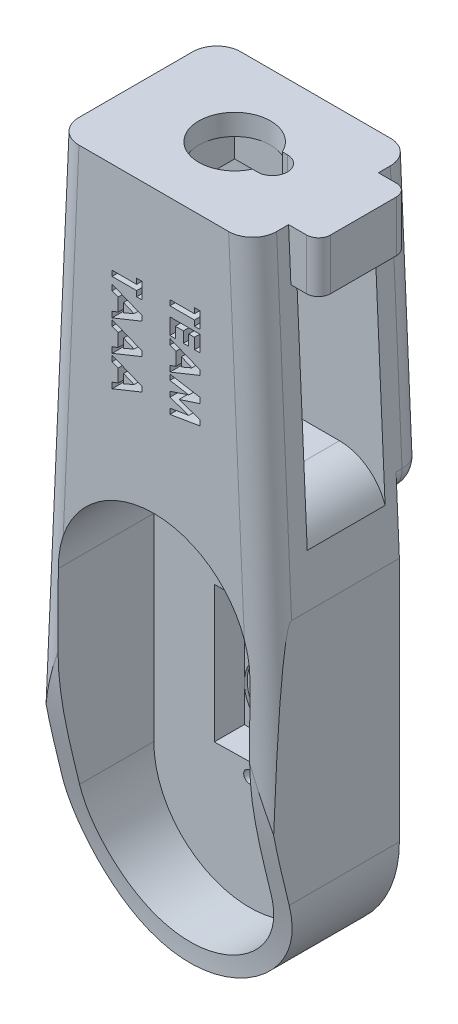
SolidWorks part; units mm, degrees
ref_plane "Front Plane" through (0, 0, 0) normal (0, 0, 1) x (1, 0, 0)
ref_plane "Top Plane" through (0, 0, 0) normal (0, 1, 0) x (1, 0, 0)
ref_plane "Right Plane" through (0, 0, 0) normal (1, 0, 0) x (0, 0, -1)
sketch "Sketch1" plane through (0, 0, 0) normal (0, 0, 1) x (1, 0, 0)
  line L5 (-19, -60) -> (19, -60)
  line L6 (-19, -60) -> (-19, 60)
  line L7 (-19, 60) -> (19, 60)
  line L8 (19, -60) -> (19, 60)
  dimension "D4" = 120
extrude "Boss-Extrude1" add sketch "Sketch1" along normal blind 11
ref_plane "Plane1" through (0, 0, 10) normal (0, 0, 1) x (1, 0, 0)
fillet "Fillet3" radius 19 2 edges at (19, -60, 5.5) (-19, -60, 5.5)
sketch "Sketch4" plane through (0, 0, 11) normal (0, 0, 1) x (1, 0, 0)
  line L0 (16, -41) -> (16, 57)
  line L1 (16, 57) -> (-16, 57)
  line L2 (-16, 57) -> (-16, -41)
  line L3 (19, -41) -> (19, 60)
  line L4 (19, 60) -> (-19, 60)
  line L5 (-19, 60) -> (-19, -41)
  line L6 (19, -41) -> (19, 60)
  line L7 (19, 60) -> (-19, 60)
  line L8 (-19, 60) -> (-19, -41)
  arc A0 (-16, -41) -> (0, -57) centre (0, -41) ccw
  arc A1 (0, -57) -> (16, -41) centre (0, -41) ccw
  arc A2 (-19, -41) -> (0, -60) centre (0, -41) ccw
  arc A3 (0, -60) -> (19, -41) centre (0, -41) ccw
  arc A4 (-19, -41) -> (0, -60) centre (0, -41) ccw
  arc A5 (0, -60) -> (19, -41) centre (0, -41) ccw
  dimension "D1" = 0
  dimension "D2" = 3
extrude "Boss-Extrude2" add sketch "Sketch4" along normal blind 8
sketch "Sketch6" plane through (0, 0, 0) normal (1, 0, 0) x (0, 0, -1)
  line L7 (-13, -60) -> (-17, -35)
  line L8 (-17, -35) -> (-19, -20)
  line L9 (-19, -41) -> (-19, 60) construction
  line L10 (-19, -20) -> (-19, -60)
  line L11 (-19, -41) -> (-19, -60) construction
  line L12 (-19, -60) -> (-13, -60)
  line L13 (-11, -60) -> (0, -60) construction
  spline S0 degree 3 poles (-19, -20) (-18.8828, -33.6175) (-12.1748, -46.2563) (-13, -60) knots 0 0 0 0 1 1 1 1
  dimension "D1" = 6
  dimension "D2" = 25
  dimension "D3" = 15
  dimension "D4" = 2
extrude "Cut-Extrude2" cut sketch "Sketch6" against normal through all both and the other way through all contours L8 L7 | L10 L12 L7 L8 region at (0, -47.6101, 16.9935) region at (0, -47.9061, 14.5246)
sketch "Sketch7" plane through (0, 0, 11) normal (0, 0, 1) x (1, 0, 0)
  line L0 (16, -20) -> (16, 57) construction
  line L1 (16, 8) -> (-16, 8)
  line L2 (16, 8) -> (16, 57)
  line L3 (16, 57) -> (-16, 57)
  line L4 (-16, 8) -> (-16, 57)
  dimension "D1" = 49
extrude "Boss-Extrude4" add sketch "Sketch7" along normal up to surface (8 mm away) up to face at (0, 19.25, 19)
sketch "Sketch8" plane through (0, 0, 0) normal (0, 0, -1) x (-1, 0, 0)
  line L0 (-19, 60) -> (19, 60)
  line L1 (19, 60) -> (19, -6.3108)
  line L2 (19, 60) -> (19, -41) construction
  line L3 (-19, 60) -> (-19, -7)
  line L4 (-19, -41) -> (-19, 60) construction
  line L7 (19, 8) -> (-19, 8)
  arc A0 (19, -6.3108) -> (-19, -7) centre (0.25, -20.4388) ccw
  line M2 (-19, 60) -> (-19, -41)
  line M6 (19, 60) -> (-19, 60)
  dimension "D1" = 23.4769
  dimension "D2" = 67
  dimension "D3" = 19.25
  dimension "D4" = 52
extrude "Boss-Extrude5" add sketch "Sketch8" along normal blind 8 contours L7 L1 M6 M2 region at (0, 34, 0)
sketch "Sketch24" plane through (0, 0, 0) normal (0, 0, -1) x (-1, 0, 0)
  line L3 (-19, 8) -> (-19, -41)
  line L4 (19, -41) -> (19, 8)
  line L5 (19, 8) -> (-19, 8)
  line L6 (-19, 8) -> (-19, -41)
  line L7 (19, -41) -> (19, 8)
  line L9 (19, 8) -> (-19, 8)
  arc A3 (-19, -41) -> (0, -60) centre (0, -41) ccw
  arc A6 (-19, -41) -> (0, -60) centre (0, -41) ccw
  arc A7 (0, -60) -> (19, -41) centre (0, -41) ccw
  arc A8 (0, -60) -> (19, -41) centre (0, -41) ccw
  dimension "D1" = 0
extrude "Boss-Extrude6" add sketch "Sketch24" along normal blind 3
sketch "Sketch3" plane through (0, 0, 10) normal (0, 0, 1) x (1, 0, 0)
  circle A6 centre (0, -10.975) radius 1
  circle A7 centre (0, -38.125) radius 1
  dimension "D1" = 10.975
  dimension "D2" = 27.15
extrude "Cut-Extrude1" cut sketch "Sketch3" against normal through all both and the other way through all
fillet "Fillet4" radius 16 2 edges at (-16, 8, 15) (16, 8, 15)
sketch "Sketch26" plane through (0, 60, 0) normal (0, 1, 0) x (1, 0, 0)
  line L4 (19, -19) -> (19, 8)
  line L5 (19, 8) -> (-19, 8)
  line L6 (-19, 8) -> (-19, -19)
  line L7 (-19, -19) -> (19, -19)
  line L8 (19, -19) -> (19, 8)
  line L10 (-19, 8) -> (-19, -19)
  line L11 (-19, -19) -> (19, -19)
  line L23 (19, 8) -> (-19, 8)
  dimension "D1" = 0
extrude "Cut-Extrude4" cut sketch "Sketch26" against normal blind 5
sketch "Sketch27" plane through (19, 0, 0) normal (1, 0, 0) x (0, 0, -1)
  line L0 (-19, 55) -> (8, 55) construction
  line L1 (-12, 45) -> (1, 45)
  line L2 (-12, 45) -> (-12, 14)
  line L3 (-12, 14) -> (1, 14)
  line L4 (1, 45) -> (1, 14)
  line L5 (-19, -20) -> (-19, 55) construction
  dimension "D1" = 10
  dimension "D2" = 31
  dimension "D3" = 13
  dimension "D4" = 7
extrude "Cut-Extrude5" cut sketch "Sketch27" against normal through all
sketch "Sketch29" plane through (0, 45, 0) normal (0, -1, 0) x (1, 0, 0)
  line L7 (-19, -1) -> (19, -1)
  line L8 (19, -1) -> (19, 12)
  line L9 (19, 19) -> (19, -8) construction
  line L10 (19, 12) -> (-19, 12)
  line L11 (-19, 12) -> (-19, -1)
extrude "Cut-Extrude7" cut sketch "Sketch29" against normal blind 1.5
sketch "Sketch28" plane through (0, 55, 0) normal (0, 1, 0) x (1, 0, 0)
  line L0 (-19, 8) -> (-19, -19) construction
  line L1 (19, 8) -> (-19, 8) construction
  line L2 (0, -5.5) -> (8.8, -5.5)
  line L3 (6.3, -3) -> (5.4544, -3)
  line L4 (6.3, -8) -> (5.4544, -8)
  arc A0 (5.4544, -3) -> (5.4544, -8) centre (0, -5.5) ccw
  arc A1 (6.3, -8) -> (6.3, -3) centre (6.3, -5.5) ccw
  dimension "D1" = 12
  dimension "D4" = 6.3
  dimension "D2" = 19
  dimension "D3" = 13.5
extrude "Cut-Extrude8" cut sketch "Sketch28" against normal blind 3.5 contours A0 L4 A1 L3
fillet "Fillet6" radius 8 2 edges at (-19, 14, 5.5) (19, 14, 5.5)
sketch "Sketch34" plane through (0, 0, 19) normal (0, 0, 1) x (1, 0, 0)
  line L0 (16.5, 55) -> (19, 0)
  line L1 (-19, 55) -> (19, 55) construction
  line L2 (19, -20) -> (19, 55) construction
  line L3 (19, 0) -> (19, 55)
  line L4 (19, 55) -> (16.5, 55)
  line L5 (-16.5, 55) -> (-19, 0)
  line L6 (-19, 55) -> (-19, -20) construction
  line L7 (-19, 0) -> (-19, 55)
  line L8 (-19, 55) -> (-16.5, 55)
  dimension "D1" = 2.5
  dimension "D2" = 2.5
  dimension "D3" = 55
  dimension "D4" = 55
extrude "Cut-Extrude13" cut sketch "Sketch34" against normal through all
fillet "Fillet11" radius 4 4 edges at (-17.5682, 31.5, -8) (-17.75, 27.5, 19) (17.5682, 31.5, -8) (17.75, 27.5, 19)
sketch "Sketch35" plane through (0, 0, 19) normal (0, 0, 1) x (1, 0, 0)
  line L0 (2.684, 8) -> (2.684, 55) construction
  text T0 "<b>TEAM </b>\r\n<b>TAAA</b>\r\n" font "Century Gothic" height 5
extrude "Cut-Extrude14" cut sketch "Sketch35" against normal blind 2.5
fillet "Fillet12" radius 4 5 edges at (-18.6364, 8, -3.5) (-17.4636, 8, -6.8284) (18.6364, 8, -3.5) (17.4636, 8, -6.8284) (0, 8, -8)
sketch "Sketch39" plane through (0, 46.5, 0) normal (0, -1, 0) x (1, 0, 0)
  line L3 (-6, -0.5) -> (0, -0.5)
  line L4 (0, -0.5) -> (16.5, -0.5)
  line L5 (16.5, -4) -> (16.5, 15) construction
  line L7 (16.5, 11.4993) -> (0.0905, 11.4993)
  line L8 (-6, 11.5) -> (-6, -0.5)
  line L9 (16.5, 5.5) -> (16.6, 5.5)
  line L12 (16.5, 11.4993) -> (21.3, 11.4993)
  line L13 (21.3, 11.4993) -> (21.3, -0.5)
  line L14 (21.3, -0.5) -> (16.5, -0.5)
  line L15 (0.0905, 11.4993) -> (-6, 11.5)
  arc A0 (5.4544, 8) -> (5.4544, 3) centre (0, 5.5) ccw construction
  arc A1 (5.4544, 8) -> (5.4544, 3) centre (0, 5.5) ccw construction
extrude "Cut-Extrude16" cut sketch "Sketch39" against normal blind 5 contours L7 L15 L8 L3 L4 L14 L12 region at (5.4431, 46.5, 5.4997)
sketch "Sketch40" plane through (0, 55, 0) normal (0, 1, 0) x (1, 0, 0)
  line L6 (16.5, -5.5) -> (16.5, -13)
  line L7 (16.5, 4) -> (16.5, -15) construction
  line L8 (16.5, -13) -> (21.5, -13)
  line L9 (21.5, -13) -> (21.5, 2)
  line L10 (21.5, 2) -> (16.5, 2)
  line L11 (16.5, 2) -> (16.5, -5.5)
extrude "Boss-Extrude8" add sketch "Sketch40" against normal blind 8.5
sketch "Sketch32" plane through (0, 46.5, 0) normal (0, -1, 0) x (1, 0, 0)
  line L0 (0, 5.5) -> (-8.5, 5.5)
  line L2 (0, 5.5) -> (19, 5.5)
  circle A0 centre (19, 5.5) radius 1.1
  circle A1 centre (-8.5, 5.5) radius 1.1
  dimension "D1" = 2.2
  dimension "D2" = 2.2
extrude "Cut-Extrude11" cut sketch "Sketch32" against normal mid plane 5 contours A0 | A1
fillet "Fillet13" radius 2 2 edges at (21.5, 50.75, -2) (21.5, 50.75, 13)
sketch "Sketch44" plane through (0, 0, 11) normal (0, 0, 1) x (1, 0, 0)
  line L2 (-16, -8) -> (-16, -41)
  line L3 (16, -41) -> (16, -8)
  line L4 (-16, -8) -> (-16, -41)
  line L5 (16, -41) -> (16, -8)
  arc A3 (16, -8) -> (0, 8) centre (0, -8) ccw
  arc A4 (0, 8) -> (-16, -8) centre (0, -8) ccw
  arc A5 (-16, -41) -> (16, -41) centre (0, -41) ccw
  arc A6 (16, -8) -> (0, 8) centre (0, -8) ccw
  arc A7 (0, 8) -> (-16, -8) centre (0, -8) ccw
  arc A8 (-16, -41) -> (16, -41) centre (0, -41) ccw
  dimension "D1" = 0
extrude "Cut-Extrude17" cut sketch "Sketch44" against normal blind 5 from offset 3 offset against normal yes
sketch "Sketch47" plane through (0, 0, 3) normal (0, 0, 1) x (1, 0, 0)
  line L10 (6.1, -35.8) -> (-5.9, -36.0017)
  line L16 (-2.3823, -23.6002) -> (-2.4, -24.4456)
  line L17 (2.6177, -23.6002) -> (2.6, -24.4456)
  line L18 (-5.9, -36.0017) -> (-5.9, -13.2)
  line L19 (-5.9, -13.2) -> (6.1, -13.2)
  line L20 (6.1, -13.2) -> (6.1, -35.8)
  arc A5 (-2.3823, -23.6002) -> (2.6177, -23.6002) centre (0.1177, -23.6002) cw
  arc A6 (2.6, -24.4456) -> (-2.4, -24.4456) centre (0.1, -29.9) cw
  dimension "D8" = 13.2
  dimension "D11" = 6
  dimension "D12" = 2.5
  dimension "D9" = 22.6
  dimension "D10" = 12
  dimension "D13" = 0.8455
  dimension "D14" = 0.8455
  dimension "D15" = 6.2998
extrude "Cut-Extrude18" cut sketch "Sketch47" against normal offset from surface 1 and the other way through all contours L18 A6 L16 A5 L17 L20 L19 | L10 A6 L18 | L20 A6 L10 | A6 L17 A5 L16 up to face at (0, -7.7932, -3)
extrude "Cut-Extrude19" cut sketch "Sketch47<3>" against normal offset from surface (5.5 mm away) 0.5 contours A6 L17 A5 L16 up to face at (0, -7.7932, -3)
sketch "Sketch47<3>" plane through (0, 0, 3) normal (0, 0, 1) x (1, 0, 0) same geometry as "Sketch47"
sketch "Sketch49" plane through (0, 0, 11) normal (0, 0, 1) x (1, 0, 0)
  line L2 (-16, -8) -> (-16, -41)
  line L3 (16, -41) -> (16, -8)
  line L4 (-16, -8) -> (-16, -41)
  line L5 (16, -41) -> (16, -8)
  arc A3 (16, -8) -> (0, 8) centre (0, -8) ccw
  arc A4 (0, 8) -> (-16, -8) centre (0, -8) ccw
  arc A5 (-16, -41) -> (16, -41) centre (0, -41) ccw
  arc A6 (16, -8) -> (0, 8) centre (0, -8) ccw
  arc A7 (0, 8) -> (-16, -8) centre (0, -8) ccw
  arc A8 (-16, -41) -> (16, -41) centre (0, -41) ccw
  dimension "D1" = 0
extrude "Cut-Extrude21" cut sketch "Sketch49" against normal blind 3
sketch "Sketch50" plane through (0, 0, -2.5) normal (0, 0, 1) x (1, 0, 0)
  circle A0 centre (0.1, -29.9) radius 2.3
  dimension "D1" = 4.6
extrude "Cut-Extrude22" cut sketch "Sketch50" against normal blind 3
